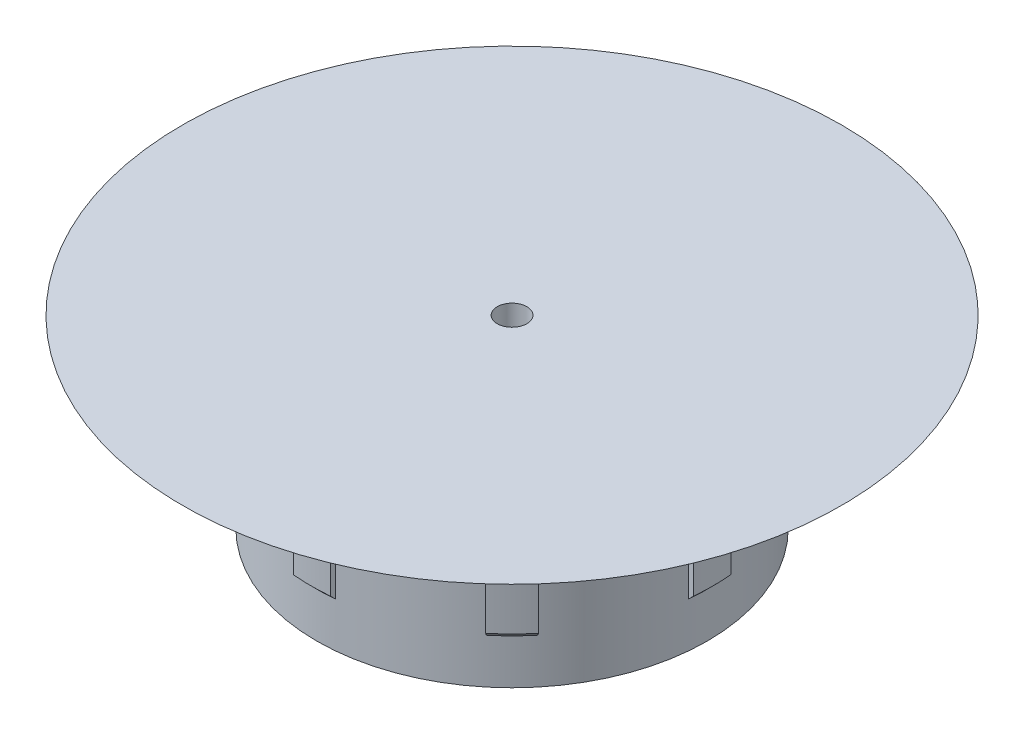
SolidWorks part; units mm, degrees
ref_plane "Front Plane" through (0, 0, 0) normal (0, 0, 1) x (1, 0, 0)
ref_plane "Top Plane" through (0, 0, 0) normal (0, 1, 0) x (1, 0, 0)
ref_plane "Right Plane" through (0, 0, 0) normal (1, 0, 0) x (0, 0, -1)
sketch "Sketch1" plane through (0, 0, 0) normal (0, 0, 1) x (1, 0, 0)
  line L0 (0, 0) -> (0, 23.3158) construction
  line L1 (23.2283, 15.24) -> (38.1, 21.336)
  line L2 (0, 0) -> (23.2283, 0)
  line L3 (0, 0) -> (0, 15.24)
  line L4 (0, 15.24) -> (23.2283, 15.24)
  line L5 (23.2283, 0) -> (23.2283, 15.24)
  line L6 (38.1, 21.336) -> (0, 21.336)
  dimension "D1" = 76.2
  dimension "D2" = 6.096
  dimension "D3" = 15.24
  dimension "D4" = 46.4566
revolve "Revolve1" add sketch "Sketch1" angle 360 about L0 region at (11.6142, 7.62, 0) region at (15.6326, 18.5344, 0)
sketch "Sketch2" plane through (0, 0, 0) normal (0, -1, 0) x (1, 0, 0)
  line L0 (0, 0) -> (0, 23.2283) construction
  line L1 (0, 0) -> (-2.159, 23.1277)
  line L2 (0, 0) -> (2.159, 23.1277)
  line L3 (0, 0) -> (14.8271, 17.8804)
  line L4 (0, 0) -> (17.8804, 14.8271)
  line L5 (0, 0) -> (23.1277, 2.159)
  line L6 (0, 0) -> (23.1277, -2.159)
  line L7 (0, 0) -> (17.8804, -14.8271)
  line L8 (0, 0) -> (14.8271, -17.8804)
  line L9 (0, 0) -> (2.159, -23.1277)
  line L10 (0, 0) -> (-2.159, -23.1277)
  line L11 (0, 0) -> (-14.8271, -17.8804)
  line L12 (0, 0) -> (-17.8804, -14.8271)
  line L13 (0, 0) -> (-23.1277, -2.159)
  line L14 (0, 0) -> (-23.1277, 2.159)
  line L15 (0, 0) -> (-17.8804, 14.8271)
  line L16 (0, 0) -> (-14.8271, 17.8804)
  circle A0 centre (0, 0) radius 22.5806
  circle A2 centre (0, 0) radius 23.2283 construction
  circle A3 centre (0, 0) radius 23.2283 construction
  circle A4 centre (0, 0) radius 23.2283
  circle A6 centre (0, 0) radius 23.2283
  point P29 (0, 0)
  circle M5 centre (0, 0) radius 23.2283
  dimension "D2" = 0.6477
  dimension "D1" = 4.318
  dimension "D3" = 0
  dimension "D4" = 8
extrude "Cut-Extrude1" cut sketch "Sketch2" against normal blind 15.24 contours A0 L3 L2 M5 | A0 L1 L16 M5 | A0 L15 L14 M5 | A0 L13 L12 M5 | A0 L11 L10 M5 | A0 L9 L8 M5 | A0 L7 L6 M5 | A0 L5 L4 M5 region at (-8.6947, 0, 20.9908) region at (2.2679, 0, 22.7923) region at (17.7203, 0, 14.5129) region at (22.7923, 0, -2.2679) region at (14.5129, 0, -17.7203) region at (-2.2679, 0, -22.7923) region at (-17.7203, 0, -14.5129) region at (-22.7923, 0, 2.2679)
sketch "Sketch3" plane through (0, 21.336, 0) normal (0, 1, 0) x (1, 0, 0)
  circle A0 centre (0, 0) radius 1.71
  dimension "D1" = 3.42
extrude "Cut-Extrude2" cut sketch "Sketch3" against normal blind 15.24
sketch "Sketch4" plane through (0, 0, 0) normal (0, -1, 0) x (1, 0, 0)
  circle A0 centre (0, 0) radius 22.5806
  circle A1 centre (0, 0) radius 23.2283
extrude "Cut-Extrude3" cut sketch "Sketch4" against normal blind 5.08
chamfer "Chamfer1" distance 0.762 angle 45 8 edges at (0, 5.08, -23.2283) (16.4249, 5.08, -16.4249) (23.2283, 5.08, 0) (16.4249, 5.08, 16.4249) (0, 5.08, 23.2283) (-16.4249, 5.08, 16.4249) (-23.2283, 5.08, 0) (-16.4249, 5.08, -16.4249)
